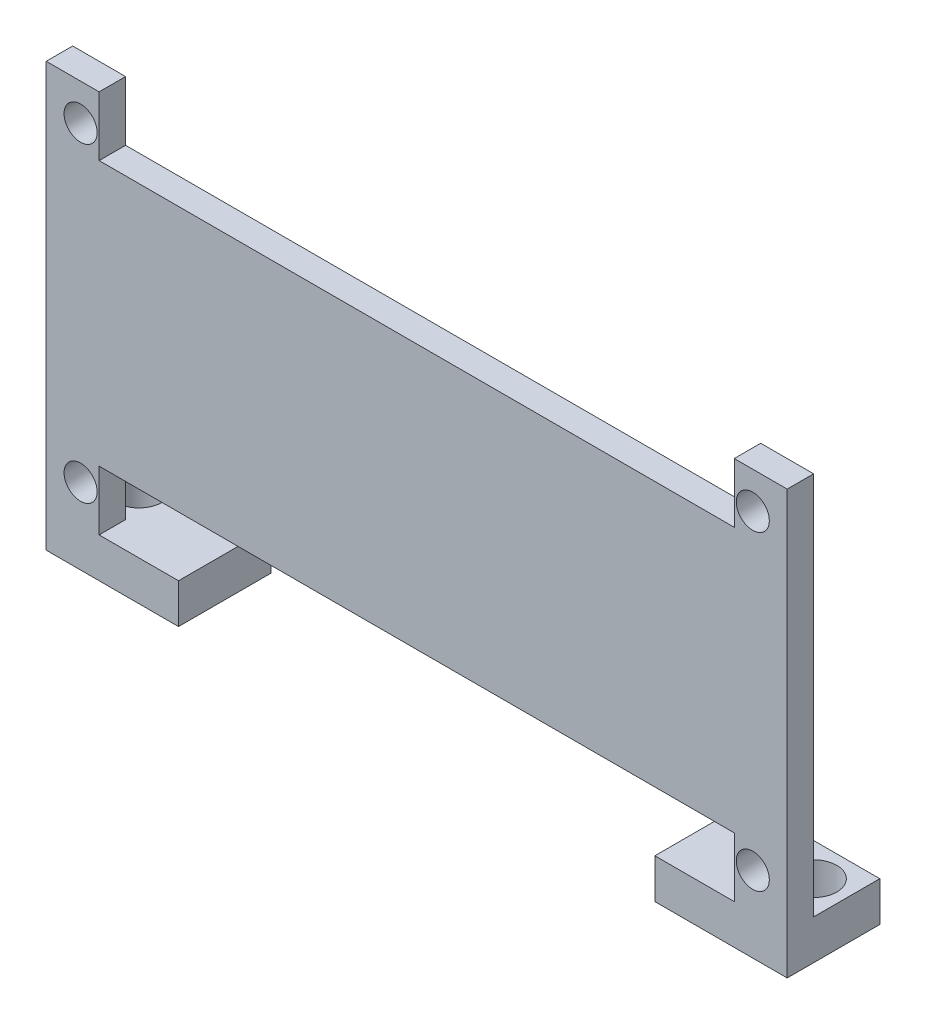
SolidWorks part; units mm, degrees
ref_plane "Plano frontal" through (0, 0, 0) normal (0, 0, 1) x (1, 0, 0)
ref_plane "Plano superior" through (0, 0, 0) normal (0, 1, 0) x (1, 0, 0)
ref_plane "Plano direito" through (0, 0, 0) normal (1, 0, 0) x (0, 0, -1)
sketch "Esboço1" plane through (0, 0, 0) normal (0, 0, 1) x (1, 0, 0)
  line L22 (-13.9657, 17.1176) -> (-13.9657, -11.8824)
  line L28 (-9.9657, 12.6176) -> (38.0343, 12.6176)
  line L33 (-9.9657, -7.3824) -> (38.0343, -7.3824)
  line L35 (42.0343, -11.8824) -> (42.0343, 17.1176)
  line L36 (-13.9657, 17.1176) -> (-9.9657, 17.1176)
  line L37 (42.0343, -11.8824) -> (38.0343, -11.8824)
  line L38 (-9.9657, 12.6176) -> (-9.9657, 17.1176)
  line L39 (38.0343, 12.6176) -> (38.0343, 17.1176)
  line L40 (38.0343, -7.3824) -> (38.0343, -11.8824)
  line L41 (-9.9657, -7.3824) -> (-9.9657, -11.8824)
  line L42 (38.0343, 17.1176) -> (42.0343, 17.1176)
  line L43 (-9.9657, -11.8824) -> (-13.9657, -11.8824)
  circle A0 centre (-11.3657, 14.3676) radius 1.25
  circle A1 centre (-11.3657, -9.1324) radius 1.25
  circle A2 centre (39.4343, -9.1324) radius 1.25
  circle A3 centre (39.4343, 14.3676) radius 1.25
  dimension "D12" = 2.75
  dimension "D9" = 2.6
  dimension "D1" = 48
  dimension "D2" = 20
  dimension "D5" = 4.5
  dimension "D6" = 4.5
  dimension "D7" = 56
  dimension "D8" = 29
  dimension "D10" = 2.75
  dimension "D11" = 2.6
  dimension "D13" = 2.75
  dimension "D14" = 2.6
  dimension "D15" = 2.75
  dimension "D16" = 2.6
extrude "Ressalto-extrusão1" add sketch "Esboço1" along normal blind 2 contours L43 L41 L33 L40 L37 L35 L42 L39 L28 L38 L36 L22 A3 A2 A1 A0 region at (14.0343, 2.6176, 0)
sketch "Esboço3" plane through (0, 0, 2) normal (0, 0, 1) x (1, 0, 0)
  line L0 (-3.9657, -11.8824) -> (-3.9657, -14.8824)
  line L1 (-13.9657, -11.8824) -> (-3.9657, -11.8824)
  line L2 (-13.9657, -11.8824) -> (-13.9657, -14.8824)
  line L3 (-13.9657, -14.8824) -> (-3.9657, -14.8824)
  line L4 (42.0343, -11.8824) -> (42.0343, -14.8824)
  line L6 (32.0343, -14.8824) -> (32.0343, -11.8824)
  line L7 (32.0343, -11.8824) -> (42.0343, -11.8824)
  line L8 (32.0343, -14.8824) -> (42.0343, -14.8824)
  dimension "D1" = 3
  dimension "D2" = 10
  dimension "D3" = 10
extrude "Ressalto-extrusão2" add sketch "Esboço3" against normal blind 7
sketch "Esboço4" plane through (0, -11.8824, 0) normal (0, 1, 0) x (1, 0, 0)
  line L0 (-13.9657, 5) -> (-13.9657, 0) construction
  line L1 (-3.9657, 5) -> (-13.9657, 5) construction
  line L2 (42.0343, 5) -> (42.0343, 0) construction
  line L3 (42.0343, 5) -> (32.0343, 5) construction
  circle A0 centre (-11.4657, 2.5) radius 1.75
  circle A1 centre (39.5343, 2.5) radius 1.75
  dimension "D1" = 3.5
  dimension "D2" = 2.5
  dimension "D3" = 2.5
  dimension "D4" = 2.5
  dimension "D5" = 2.5
extrude "Corte-extrusão1" cut sketch "Esboço4" against normal blind 5
